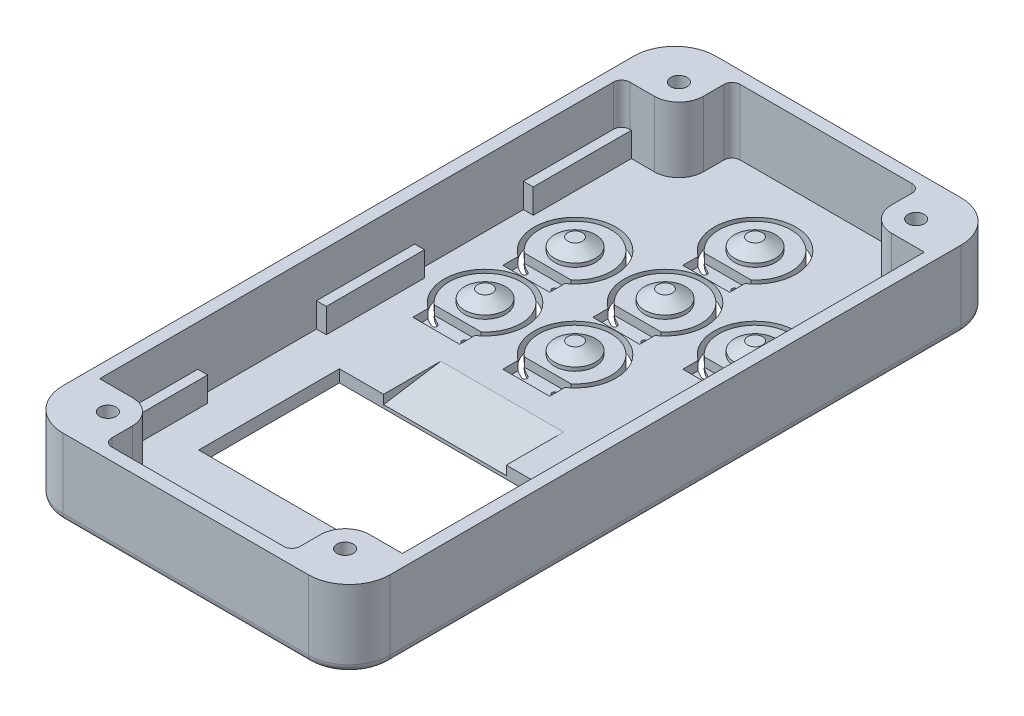
SolidWorks part; units mm, degrees
ref_plane "Front Plane" through (0, 0, 0) normal (0, 0, 1) x (1, 0, 0)
ref_plane "Top Plane" through (0, 0, 0) normal (0, 1, 0) x (1, 0, 0)
ref_plane "Right Plane" through (0, 0, 0) normal (1, 0, 0) x (0, 0, -1)
sketch "Base Sketch" plane through (0, 0, 0) normal (0, 1, 0) x (1, 0, 0)
  line L0 (0, 0) -> (40, 0)
  line L1 (40, 0) -> (40, 79.79)
  line L2 (40, 79.79) -> (0, 79.79)
  line L3 (0, 79.79) -> (0, 0)
extrude "Base" add sketch "Base Sketch" along normal blind 9.5
fillet "Corner Rounds R5" radius 5 4 edges at (0, 4.75, -79.79) (40, 4.75, -79.79) (40, 4.75, 0) (0, 4.75, 0)
shell "Shell 1.5" thickness 1.5 removed face at (20, 9.5, -39.895)
sketch "Boss Sketch" plane through (0, 0, 0) normal (0, 1, 0) x (1, 0, 0)
  line L0 (1.5, 1.5) -> (8.5, 1.5)
  line L1 (8.5, 1.5) -> (8.5, 5)
  line L2 (5.5, 8) -> (1.5, 8)
  line L3 (1.5, 8) -> (1.5, 1.5)
  line L4 (38.5, 1.5) -> (31.5, 1.5)
  line L5 (31.5, 1.5) -> (31.5, 5)
  line L6 (34.5, 8) -> (38.5, 8)
  line L7 (38.5, 8) -> (38.5, 1.5)
  line L16 (1.5, 78.29) -> (8.5, 78.29)
  line L17 (8.5, 78.29) -> (8.5, 74.79)
  line L18 (5.5, 71.79) -> (1.5, 71.79)
  line L19 (1.5, 71.79) -> (1.5, 78.29)
  line L20 (38.5, 78.29) -> (31.5, 78.29)
  line L21 (31.5, 78.29) -> (31.5, 74.79)
  line L22 (34.5, 71.79) -> (38.5, 71.79)
  line L23 (38.5, 71.79) -> (38.5, 78.29)
  arc A0 (8.5, 5) -> (5.5, 8) centre (5.4999, 4.9999) ccw
  circle A1 centre (5.5, 5) radius 1
  arc A2 (31.5, 5) -> (34.5, 8) centre (34.5001, 4.9999) cw
  circle A3 centre (34.5, 5) radius 1
  circle A5 centre (5.5, 74.79) radius 1
  circle A7 centre (34.5, 74.79) radius 1
  arc A8 (8.5, 74.79) -> (5.5, 71.79) centre (5.4999, 74.7901) cw
  arc A9 (31.5, 74.79) -> (34.5, 71.79) centre (34.5001, 74.7901) ccw
extrude "Corner Bosses + M2 Pilot Holes" add sketch "Boss Sketch" along normal blind 9.5
sketch "Ledge Sketch" plane through (0, 0, 0) normal (0, 1, 0) x (1, 0, 0)
  line L0 (1.5, 8) -> (2.7, 8)
  line L1 (2.7, 8) -> (2.7, 20)
  line L2 (2.7, 20) -> (1.5, 20)
  line L3 (1.5, 20) -> (1.5, 8)
  line L4 (37.3, 8) -> (38.5, 8)
  line L5 (38.5, 8) -> (38.5, 20)
  line L6 (38.5, 20) -> (37.3, 20)
  line L7 (37.3, 20) -> (37.3, 8)
  line L8 (1.5, 34.5) -> (2.7, 34.5)
  line L9 (2.7, 34.5) -> (2.7, 46.5)
  line L10 (2.7, 46.5) -> (1.5, 46.5)
  line L11 (1.5, 46.5) -> (1.5, 34.5)
  line L12 (37.3, 34.5) -> (38.5, 34.5)
  line L13 (38.5, 34.5) -> (38.5, 46.5)
  line L14 (38.5, 46.5) -> (37.3, 46.5)
  line L15 (37.3, 46.5) -> (37.3, 34.5)
  line L16 (1.5, 59.79) -> (2.7, 59.79)
  line L17 (2.7, 59.79) -> (2.7, 71.79)
  line L18 (2.7, 71.79) -> (1.5, 71.79)
  line L19 (1.5, 71.79) -> (1.5, 59.79)
  line L20 (37.3, 59.79) -> (38.5, 59.79)
  line L21 (38.5, 59.79) -> (38.5, 71.79)
  line L22 (38.5, 71.79) -> (37.3, 71.79)
  line L23 (37.3, 71.79) -> (37.3, 59.79)
extrude "Side Ledges" add sketch "Ledge Sketch" along normal blind 4.5
fillet "Outer Face Round R1" radius 1 8 edges at (1.4645, 0, -1.4645) (20, 0, 0) (38.5355, 0, -1.4645) (40, 0, -39.895) (38.5355, 0, -78.3255) (20, 0, -79.79) (1.4645, 0, -78.3255) (0, 0, -39.895)
sketch "Window Sketch" plane through (0, 0, 0) normal (0, 1, 0) x (1, 0, 0)
  line L0 (7.1, 14.5) -> (32.9, 14.5)
  line L1 (32.9, 14.5) -> (32.9, 31.7)
  line L2 (32.9, 31.7) -> (7.1, 31.7)
  line L3 (7.1, 31.7) -> (7.1, 14.5)
extrude "Display Window" cut sketch "Window Sketch" along normal through all
ref_plane "Mid Plane X20" through (20, 0, 0) normal (1, 0, 0) x (0, 0, -1)
sketch "Ramp Sketch" plane through (20, 0, 0) normal (1, 0, 0) x (0, 0, -1)
  line L0 (31, 0.4) -> (31.7, 0.4)
  line L1 (31.7, 0.4) -> (38.7, 1.5)
  line L2 (38.7, 1.5) -> (38.7, 2.5)
  line L3 (38.7, 2.5) -> (31, 2.5)
  line L4 (31, 2.5) -> (31, 0.4)
extrude "Cable Ramp" cut sketch "Ramp Sketch" against normal blind 7.5 and the other way blind 7.5
ref_plane "Plate Inner Face" through (0, 1.5, 0) normal (0, 1, 0) x (1, 0, 0)
sketch "LED Window Sketch" plane through (0, 1.5, 0) normal (0, 1, 0) x (1, 0, 0)
  circle A0 centre (20, 7.28) radius 1.75
extrude "LED Window" cut sketch "LED Window Sketch" against normal blind 1.3
sketch "Plunger Stems Sketch" plane through (0, 1.5, 0) normal (0, 1, 0) x (1, 0, 0)
  circle A0 centre (9, 47.6) radius 2.5
  circle A1 centre (20, 47.6) radius 2.5
  circle A2 centre (9, 58.6) radius 2.5
  circle A3 centre (20, 58.6) radius 2.5
  circle A4 centre (31, 58.6) radius 2.5
  circle A5 centre (20, 69.6) radius 2.5
extrude "Plunger Stems 5.0" add sketch "Plunger Stems Sketch" along normal blind 0.45
ref_plane "Plunger Cone Base" through (0, 1.95, 0) normal (0, 1, 0) x (1, 0, 0)
sketch "Plunger Cone Sketch" plane through (0, 1.95, 0) normal (0, 1, 0) x (1, 0, 0)
  circle A0 centre (9, 47.6) radius 2.5
  circle A1 centre (20, 47.6) radius 2.5
  circle A2 centre (9, 58.6) radius 2.5
  circle A3 centre (20, 58.6) radius 2.5
  circle A4 centre (31, 58.6) radius 2.5
  circle A5 centre (20, 69.6) radius 2.5
extrude "Plunger Cones to 1.8" add sketch "Plunger Cone Sketch" along normal blind 1 draft 57.995
sketch "C-Slot Sketch" plane through (0, 0, 0) normal (0, 1, 0) x (1, 0, 0)
  arc A0 (10.9149, 42.9812) -> (7.0851, 42.9812) centre (9, 47.6) ccw
  arc A1 (7.0851, 42.9812) -> (7.3149, 43.5355) centre (7.2, 43.2583) ccw
  arc A2 (7.3149, 43.5355) -> (10.6851, 43.5355) centre (9, 47.6) cw
  arc A3 (10.6851, 43.5355) -> (10.9149, 42.9812) centre (10.8, 43.2583) ccw
  arc A4 (21.9149, 42.9812) -> (18.0851, 42.9812) centre (20, 47.6) ccw
  arc A5 (18.0851, 42.9812) -> (18.3149, 43.5355) centre (18.2, 43.2583) ccw
  arc A6 (18.3149, 43.5355) -> (21.6851, 43.5355) centre (20, 47.6) cw
  arc A7 (21.6851, 43.5355) -> (21.9149, 42.9812) centre (21.8, 43.2583) ccw
  arc A8 (10.9149, 53.9812) -> (7.0851, 53.9812) centre (9, 58.6) ccw
  arc A9 (7.0851, 53.9812) -> (7.3149, 54.5355) centre (7.2, 54.2583) ccw
  arc A10 (7.3149, 54.5355) -> (10.6851, 54.5355) centre (9, 58.6) cw
  arc A11 (10.6851, 54.5355) -> (10.9149, 53.9812) centre (10.8, 54.2583) ccw
  arc A12 (21.9149, 53.9812) -> (18.0851, 53.9812) centre (20, 58.6) ccw
  arc A13 (18.0851, 53.9812) -> (18.3149, 54.5355) centre (18.2, 54.2583) ccw
  arc A14 (18.3149, 54.5355) -> (21.6851, 54.5355) centre (20, 58.6) cw
  arc A15 (21.6851, 54.5355) -> (21.9149, 53.9812) centre (21.8, 54.2583) ccw
  arc A16 (32.9149, 53.9812) -> (29.0851, 53.9812) centre (31, 58.6) ccw
  arc A17 (29.0851, 53.9812) -> (29.3149, 54.5355) centre (29.2, 54.2583) ccw
  arc A18 (29.3149, 54.5355) -> (32.6851, 54.5355) centre (31, 58.6) cw
  arc A19 (32.6851, 54.5355) -> (32.9149, 53.9812) centre (32.8, 54.2583) ccw
  arc A20 (21.9149, 64.9812) -> (18.0851, 64.9812) centre (20, 69.6) ccw
  arc A21 (18.0851, 64.9812) -> (18.3149, 65.5355) centre (18.2, 65.2583) ccw
  arc A22 (18.3149, 65.5355) -> (21.6851, 65.5355) centre (20, 69.6) cw
  arc A23 (21.6851, 65.5355) -> (21.9149, 64.9812) centre (21.8, 65.2583) ccw
extrude "Button C-Slots" cut sketch "C-Slot Sketch" along normal through all
sketch "Hinge Sketch" plane through (0, 1.5, 0) normal (0, 1, 0) x (1, 0, 0)
  line L0 (11.1, 46.2435) -> (11.1, 42.6)
  line L1 (11.1, 42.6) -> (6.9, 42.6)
  line L2 (6.9, 42.6) -> (6.9, 46.2435)
  line L3 (6.9, 46.2435) -> (11.1, 46.2435)
  line L4 (22.1, 46.2435) -> (22.1, 42.6)
  line L5 (22.1, 42.6) -> (17.9, 42.6)
  line L6 (17.9, 42.6) -> (17.9, 46.2435)
  line L7 (17.9, 46.2435) -> (22.1, 46.2435)
  line L8 (11.1, 57.2435) -> (11.1, 53.6)
  line L9 (11.1, 53.6) -> (6.9, 53.6)
  line L10 (6.9, 53.6) -> (6.9, 57.2435)
  line L11 (6.9, 57.2435) -> (11.1, 57.2435)
  line L12 (22.1, 57.2435) -> (22.1, 53.6)
  line L13 (22.1, 53.6) -> (17.9, 53.6)
  line L14 (17.9, 53.6) -> (17.9, 57.2435)
  line L15 (17.9, 57.2435) -> (22.1, 57.2435)
  line L16 (33.1, 57.2435) -> (33.1, 53.6)
  line L17 (33.1, 53.6) -> (28.9, 53.6)
  line L18 (28.9, 53.6) -> (28.9, 57.2435)
  line L19 (28.9, 57.2435) -> (33.1, 57.2435)
  line L20 (22.1, 68.2435) -> (22.1, 64.6)
  line L21 (22.1, 64.6) -> (17.9, 64.6)
  line L22 (17.9, 64.6) -> (17.9, 68.2435)
  line L23 (17.9, 68.2435) -> (22.1, 68.2435)
extrude "Hinge Thinning 0.4" cut sketch "Hinge Sketch" against normal blind 1.1
sketch "Sketch9" plane through (0, 0.4, 0) normal (0, 1, 0) x (1, 0, 0)
  line L6 (17.9, 43.0624) -> (17.9, 42.6)
  line L7 (17.9, 42.6) -> (22.1, 42.6)
  line L8 (22.1, 42.6) -> (22.1, 43.0624)
  line L9 (22.1, 43.7335) -> (22.1, 46.2435)
  line L10 (22.1, 46.2435) -> (17.9, 46.2435)
  line L11 (17.9, 46.2435) -> (17.9, 43.7335)
  line L12 (17.9, 43.0624) -> (17.9, 42.6)
  line L13 (17.9, 42.6) -> (22.1, 42.6)
  line L14 (22.1, 42.6) -> (22.1, 43.0624)
  line L15 (22.1, 43.7335) -> (22.1, 46.2435)
  line L16 (22.1, 46.2435) -> (17.9, 46.2435)
  line L17 (17.9, 46.2435) -> (17.9, 43.7335)
  line L18 (6.9, 43.0624) -> (6.9, 42.6)
  line L19 (6.9, 42.6) -> (11.1, 42.6)
  line L20 (11.1, 42.6) -> (11.1, 43.0624)
  line L21 (11.1, 43.7335) -> (11.1, 46.2435)
  line L22 (11.1, 46.2435) -> (6.9, 46.2435)
  line L23 (6.9, 46.2435) -> (6.9, 43.7335)
  line L24 (6.9, 54.0624) -> (6.9, 53.6)
  line L25 (6.9, 53.6) -> (11.1, 53.6)
  line L26 (11.1, 53.6) -> (11.1, 54.0624)
  line L27 (11.1, 54.7335) -> (11.1, 57.2435)
  line L28 (11.1, 57.2435) -> (6.9, 57.2435)
  line L29 (6.9, 57.2435) -> (6.9, 54.7335)
  line L30 (17.9, 54.0624) -> (17.9, 53.6)
  line L31 (17.9, 53.6) -> (22.1, 53.6)
  line L32 (22.1, 53.6) -> (22.1, 54.0624)
  line L33 (22.1, 54.7335) -> (22.1, 57.2435)
  line L34 (22.1, 57.2435) -> (17.9, 57.2435)
  line L35 (17.9, 57.2435) -> (17.9, 54.7335)
  line L36 (28.9, 54.0624) -> (28.9, 53.6)
  line L37 (28.9, 53.6) -> (33.1, 53.6)
  line L38 (33.1, 53.6) -> (33.1, 54.0624)
  line L39 (33.1, 54.7335) -> (33.1, 57.2435)
  line L40 (33.1, 57.2435) -> (28.9, 57.2435)
  line L41 (28.9, 57.2435) -> (28.9, 54.7335)
  line L42 (17.9, 65.0624) -> (17.9, 64.6)
  line L43 (17.9, 64.6) -> (22.1, 64.6)
  line L44 (22.1, 64.6) -> (22.1, 65.0624)
  line L45 (22.1, 65.7335) -> (22.1, 68.2435)
  line L46 (22.1, 68.2435) -> (17.9, 68.2435)
  line L47 (17.9, 68.2435) -> (17.9, 65.7335)
  arc A6 (17.9, 43.0624) -> (18.0851, 42.9812) centre (20, 47.6) ccw
  arc A7 (21.9149, 42.9812) -> (22.1, 43.0624) centre (20, 47.6) ccw
  arc A8 (21.6851, 43.5355) -> (21.9149, 42.9812) centre (21.8, 43.2583) ccw
  arc A9 (21.6851, 43.5355) -> (22.1, 43.7335) centre (20, 47.6) ccw
  arc A10 (17.9, 43.7335) -> (18.3149, 43.5355) centre (20, 47.6) ccw
  arc A11 (18.0851, 42.9812) -> (18.3149, 43.5355) centre (18.2, 43.2583) ccw
  arc A12 (17.9, 43.0624) -> (18.0851, 42.9812) centre (20, 47.6) ccw
  arc A13 (21.9149, 42.9812) -> (22.1, 43.0624) centre (20, 47.6) ccw
  arc A14 (21.6851, 43.5355) -> (21.9149, 42.9812) centre (21.8, 43.2583) ccw
  arc A15 (21.6851, 43.5355) -> (22.1, 43.7335) centre (20, 47.6) ccw
  arc A16 (17.9, 43.7335) -> (18.3149, 43.5355) centre (20, 47.6) ccw
  arc A17 (18.0851, 42.9812) -> (18.3149, 43.5355) centre (18.2, 43.2583) ccw
  arc A18 (6.9, 43.0624) -> (7.0851, 42.9812) centre (9, 47.6) ccw
  arc A19 (10.9149, 42.9812) -> (11.1, 43.0624) centre (9, 47.6) ccw
  arc A20 (10.6851, 43.5355) -> (10.9149, 42.9812) centre (10.8, 43.2583) ccw
  arc A21 (10.6851, 43.5355) -> (11.1, 43.7335) centre (9, 47.6) ccw
  arc A22 (6.9, 43.7335) -> (7.3149, 43.5355) centre (9, 47.6) ccw
  arc A23 (7.0851, 42.9812) -> (7.3149, 43.5355) centre (7.2, 43.2583) ccw
  arc A24 (6.9, 54.0624) -> (7.0851, 53.9812) centre (9, 58.6) ccw
  arc A25 (10.9149, 53.9812) -> (11.1, 54.0624) centre (9, 58.6) ccw
  arc A26 (10.6851, 54.5355) -> (10.9149, 53.9812) centre (10.8, 54.2583) ccw
  arc A27 (10.6851, 54.5355) -> (11.1, 54.7335) centre (9, 58.6) ccw
  arc A28 (6.9, 54.7335) -> (7.3149, 54.5355) centre (9, 58.6) ccw
  arc A29 (7.0851, 53.9812) -> (7.3149, 54.5355) centre (7.2, 54.2583) ccw
  arc A30 (17.9, 54.0624) -> (18.0851, 53.9812) centre (20, 58.6) ccw
  arc A31 (21.9149, 53.9812) -> (22.1, 54.0624) centre (20, 58.6) ccw
  arc A32 (21.6851, 54.5355) -> (21.9149, 53.9812) centre (21.8, 54.2583) ccw
  arc A33 (21.6851, 54.5355) -> (22.1, 54.7335) centre (20, 58.6) ccw
  arc A34 (17.9, 54.7335) -> (18.3149, 54.5355) centre (20, 58.6) ccw
  arc A35 (18.0851, 53.9812) -> (18.3149, 54.5355) centre (18.2, 54.2583) ccw
  arc A36 (28.9, 54.0624) -> (29.0851, 53.9812) centre (31, 58.6) ccw
  arc A37 (32.9149, 53.9812) -> (33.1, 54.0624) centre (31, 58.6) ccw
  arc A38 (32.6851, 54.5355) -> (32.9149, 53.9812) centre (32.8, 54.2583) ccw
  arc A39 (32.6851, 54.5355) -> (33.1, 54.7335) centre (31, 58.6) ccw
  arc A40 (28.9, 54.7335) -> (29.3149, 54.5355) centre (31, 58.6) ccw
  arc A41 (29.0851, 53.9812) -> (29.3149, 54.5355) centre (29.2, 54.2583) ccw
  arc A42 (17.9, 65.0624) -> (18.0851, 64.9812) centre (20, 69.6) ccw
  arc A43 (21.9149, 64.9812) -> (22.1, 65.0624) centre (20, 69.6) ccw
  arc A44 (21.6851, 65.5355) -> (21.9149, 64.9812) centre (21.8, 65.2583) ccw
  arc A45 (21.6851, 65.5355) -> (22.1, 65.7335) centre (20, 69.6) ccw
  arc A46 (17.9, 65.7335) -> (18.3149, 65.5355) centre (20, 69.6) ccw
  arc A47 (18.0851, 64.9812) -> (18.3149, 65.5355) centre (18.2, 65.2583) ccw
  dimension "D1" = 0
extrude "Boss-Extrude4" add sketch "Sketch9" along normal up to surface (1.1 mm away) up to face at (20, 1.5, -67.2156)
sketch "Sketch10" plane through (0, 1.5, 0) normal (0, 1, 0) x (1, 0, 0)
  line L1 (17.1364, 44.2594) -> (22.8636, 44.2594)
  line L2 (17.1364, 44.2594) -> (17.1364, 41.6357)
  line L3 (17.1364, 41.6357) -> (22.8636, 41.6357)
  line L4 (22.8636, 44.2594) -> (22.8636, 41.6357)
  line L5 (6.1364, 44.2594) -> (11.8636, 44.2594)
  line L6 (6.1364, 44.2594) -> (6.1364, 41.6357)
  line L7 (6.1364, 41.6357) -> (11.8636, 41.6357)
  line L8 (11.8636, 44.2594) -> (11.8636, 41.6357)
  line L9 (6.1364, 55.2594) -> (11.8636, 55.2594)
  line L10 (6.1364, 55.2594) -> (6.1364, 52.6357)
  line L11 (6.1364, 52.6357) -> (11.8636, 52.6357)
  line L12 (11.8636, 55.2594) -> (11.8636, 52.6357)
  line L13 (17.1364, 55.2594) -> (22.8636, 55.2594)
  line L14 (17.1364, 55.2594) -> (17.1364, 52.6357)
  line L15 (17.1364, 52.6357) -> (22.8636, 52.6357)
  line L16 (22.8636, 55.2594) -> (22.8636, 52.6357)
  line L17 (28.1364, 55.2594) -> (33.8636, 55.2594)
  line L18 (28.1364, 55.2594) -> (28.1364, 52.6357)
  line L19 (28.1364, 52.6357) -> (33.8636, 52.6357)
  line L20 (33.8636, 55.2594) -> (33.8636, 52.6357)
  line L21 (17.1364, 66.2594) -> (22.8636, 66.2594)
  line L22 (17.1364, 66.2594) -> (17.1364, 63.6357)
  line L23 (17.1364, 63.6357) -> (22.8636, 63.6357)
  line L24 (22.8636, 66.2594) -> (22.8636, 63.6357)
  arc A0 (21.6851, 43.5355) -> (18.3149, 43.5355) centre (20, 47.6) ccw construction
extrude "Cut-Extrude7" cut sketch "Sketch10" against normal blind 1.1
fillet "Boss Junction Fillets R1" radius 1 8 edges at (1.5, 7, -71.79) (37.3, 3, -71.79) (37.3, 3, -8) (2.7, 3, -8) (31.5, 5.5, -78.29) (8.5, 5.5, -78.29) (31.5, 5.5, -1.5) (8.5, 5.5, -1.5)
